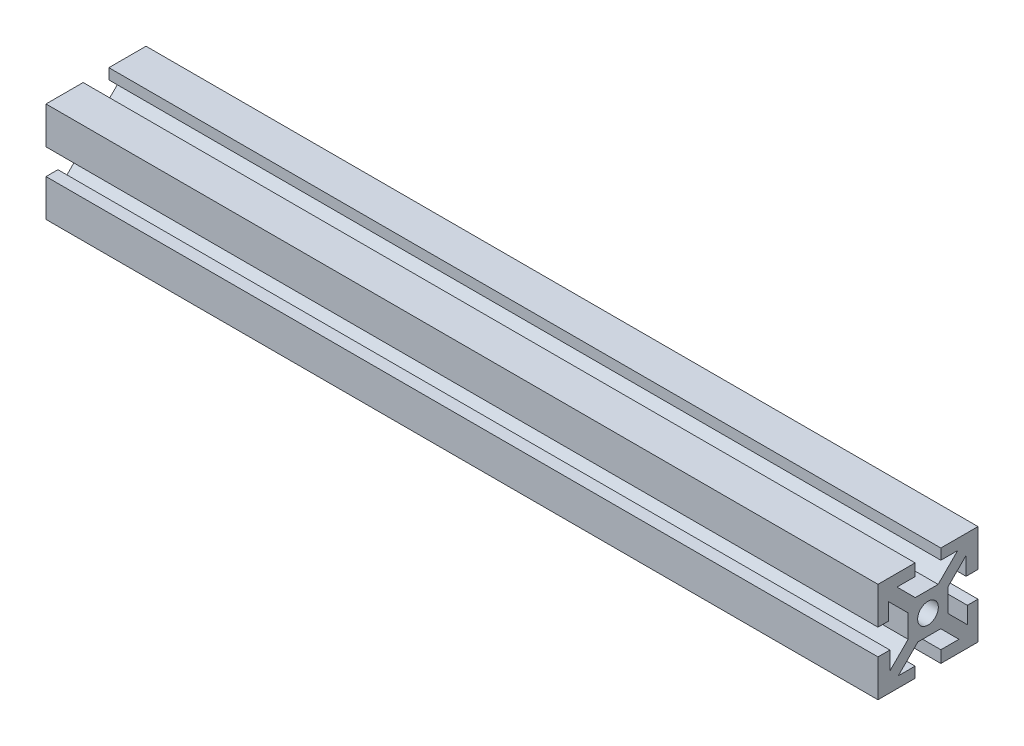
SolidWorks part; units mm, degrees
ref_plane "Front Plane" through (0, 0, 0) normal (0, 0, 1) x (1, 0, 0)
ref_plane "Top Plane" through (0, 0, 0) normal (0, 1, 0) x (1, 0, 0)
ref_plane "Right Plane" through (0, 0, 0) normal (1, 0, 0) x (0, 0, -1)
sketch "Sketch1" plane through (0, 0, 0) normal (1, 0, 0) x (0, 0, -1)
  line L0 (2.5534, 5) -> (7.4749, 9.9215)
  line L1 (-5, 5) -> (5, 5)
  line L2 (-5, 5) -> (-5, -5)
  line L3 (-5, -5) -> (5, -5)
  line L4 (5, 5) -> (5, -5)
  line L5 (-5, 5) -> (5, -5) construction
  line L6 (-5, -5) -> (5, 5) construction
  line L7 (7.4749, 9.9215) -> (9.5962, 7.8001)
  line L8 (9.5962, 7.8001) -> (5, 3.2039)
  line L9 (5, 5) -> (13.6489, 13.6489) construction
  line L10 (7.4749, 9.9215) -> (3.24, 9.9215)
  line L11 (3.24, 9.9215) -> (3.24, 12.5962)
  line L12 (3.24, 12.5962) -> (12.5962, 12.5962)
  line L13 (9.5962, 7.8001) -> (9.5962, 3.24)
  line L14 (9.5962, 3.24) -> (12.5962, 3.24)
  line L15 (12.5962, 3.24) -> (12.5962, 12.5962)
  line L17 (0, 0) -> (0, 24.089) construction
  line L18 (0, 0) -> (23.75, 0) construction
  circle A0 centre (0, 0) radius 2.605
  point P0 (0, 0)
  dimension "D1" = 5.21
  dimension "D2" = 10
  dimension "D3" = 10
  dimension "D4" = 3
  dimension "D5" = 1.27
  dimension "D6" = 6.5
  dimension "D7" = 3.24
  dimension "D8" = 3.24
  dimension "D9" = 3
extrude "Boss-Extrude1" add sketch "Sketch1" along normal blind 209.55 contours L4 L1 L2 L3 A0 | L8 L7 L0 L1 L4 | L14 L15 L12 L11 L10 L7 L13 region at (0, 4.8586, -3.7767) region at (0, 6.7479, -6.3823) region at (0, 9.18, -9.3105)
ref_axis "Axis1" through (0, 0, 0) along (1, 0, 0)
pattern_circular "CirPattern1" count 4 over 360 about axis through (0, 0, 0) along (1, 0, 0) of "Boss-Extrude1"
